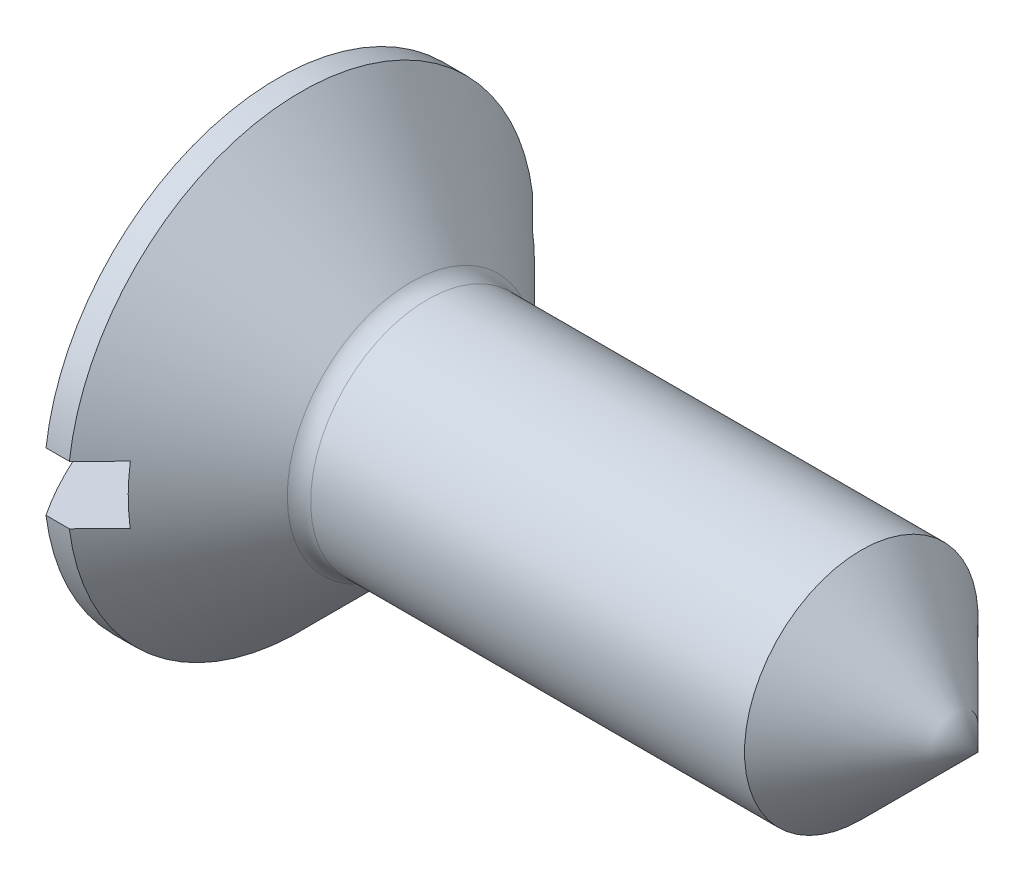
SolidWorks part; units mm, degrees
ref_plane "Front" through (0, 0, 0) normal (0, 0, 1) x (1, 0, 0)
ref_plane "Top" through (0, 0, 0) normal (0, 1, 0) x (1, 0, 0)
ref_plane "Right" through (0, 0, 0) normal (1, 0, 0) x (0, 0, -1)
sketch "Sketch2" plane through (1.6915, 0, 0.5085) normal (0, 1, 0) x (0, 0, -1)
  line L0 (0.5085, -4.3085) -> (0.5085, 2.1079) construction
  line L2 (0.5085, 0.4915) -> (1.5085, 0.4915)
  line L4 (1.5085, 0.4915) -> (2.7085, 1.6915)
  line L5 (2.7085, 1.6915) -> (0.5085, 1.6915)
  line L6 (0.5085, 0.4915) -> (0.5085, 1.6915)
  dimension "D2" = 45
revolve "BaseHead" add sketch "Sketch2" angle 360 about L0
sketch "Sketch1" plane through (1.2, 0.2435, -0.4482) normal (1, 0, 0) x (0, 0, -1)
  circle A0 centre (-0.4482, -0.2435) radius 1
extrude "BaseBody" add sketch "Sketch1" along normal blind 4.8
cosmetic thread "ThreadCosmetic1" [suppressed] parameters "D1"=3, "dm"=1.5
sketch "Sketch3" plane through (0, 0, 0) normal (1, 0, 0) x (0, 0, -1)
  circle A0 centre (0, 0) radius 2
  circle A1 centre (0, 0) radius 2.2 construction
  circle A2 centre (0, 0) radius 2.2
  dimension "dk" = 4
extrude "Cut-Extrude1" cut sketch "Sketch3" along normal through all
sketch "Sketch4" plane through (2.4858, 0, -0.4858) normal (0, 1, 0) x (0, 0, -1)
  line L0 (-0.4858, 0) -> (-0.4858, 2.9717) construction
  line L2 (-0.2358, 3.0858) -> (-0.2358, 2.4858)
  line L3 (1.5142, 2.4858) -> (-2.4858, 2.4858) construction
  line L4 (1.5142, 2.4858) -> (-0.2358, 2.4858)
  arc A0 (-0.2358, 3.0858) -> (1.5142, 2.4858) centre (-0.4892, -0.5052) cw
  dimension "rf" = 3.6
  dimension "n" = 0.5
  dimension "f" = 0.6
revolve "BaseTop" add sketch "Sketch4" angle 360 about L0
sketch "Sketch5" plane through (1.6783, 1.6783, 0) normal (0, 0, 1) x (0, 1, 0)
  line L1 (-1.4283, 1.6783) -> (-1.4283, 2.2783) construction
  line L2 (-1.6783, 0) -> (-1.6783, 3.3566) construction
  line L4 (-1.4283, 1.2183) -> (-1.9283, 1.2183)
  line L5 (-1.4283, 1.2183) -> (-1.4283, 2.2783)
  line L6 (-1.9283, 2.2783) -> (-1.9283, 1.2183)
  line L7 (-1.4283, 2.2783) -> (-1.9283, 2.2783)
  point P9 (-1.6783, 1.2183)
  dimension "t" = 1.06
extrude "Slot" cut sketch "Sketch5" against normal through all and the other way through all
fillet "Fillet1" radius 0.2 1 edges at (1.2, 0, -1)
sketch "Sketch6" plane through (12.7984, -7.2016, 0) normal (0, 0, 1) x (0, 1, 0)
  line L0 (7.2016, -3.8376) -> (7.2016, -8.4033) construction
  line L2 (7.2016, 6.0537) -> (27.2016, 6.0537)
  line L3 (27.2016, 6.0537) -> (27.2016, 26.7984)
  line L4 (27.2016, 26.7984) -> (7.2016, 6.7984)
  line L5 (7.2016, 6.7984) -> (7.2016, 6.0537)
  line L7 (6.2016, 6.7984) -> (8.2016, 6.7984) construction
  dimension "D1" = 45
  dimension "D2" = 20
  dimension "D3" = 0.7447
revolve "Cut-Revolve1" cut sketch "Sketch6" angle 360 about L0
sketch "Sketch8" plane through (0, 0, 0) normal (0, 0, 1) x (1, 0, 0)
  line L0 (2, 1.2) -> (2.25, 1.2)
  line L1 (2.25, 1.2) -> (2.25, 1)
  line L2 (2.25, 1) -> (2.125, 0.7835)
  line L3 (2, 1) -> (2.125, 0.7835)
  line L4 (2, 1.2) -> (2, 1)
  line L5 (21.5487, 0) -> (0, 0) construction
  line L6 (2, 1) -> (2.25, 1) construction
  line L7 (2.125, 1) -> (2.125, 0.7835) construction
  line L9 (5, 1) -> (1.2828, 1) construction
  point P6 (2.125, 1.2)
  dimension "D1" = 0.2
  dimension "D2" = 0.25
  dimension "D3" = 4
revolve "Cut-Revolve10" [suppressed] cut sketch "Sketch8" angle 360 about L5
pattern_linear "LPattern10" [suppressed] count 8 spacing 0.5 of bodies 107
equation "\"D1@Sketch2\" = \"d@Sketch1\" / 2"
equation "\"D2@Sketch8\" = (  \"d@Sketch1\" - \"dm@ThreadCosmetic1\" )  / 2"
equation "\"D3@Sketch8\" = \"D1@ThreadCosmetic1\" + \"d@Sketch1\" / 2"
equation "\"D3@LPattern10\" = \"D2@Sketch8\" * 2"
equation "\"D1@LPattern10\" = \"D3@Sketch8\" / \"D3@LPattern10\""
equation "\"l@BaseBody\" = \"l@Sketch2\" - \"k@Sketch2\""
